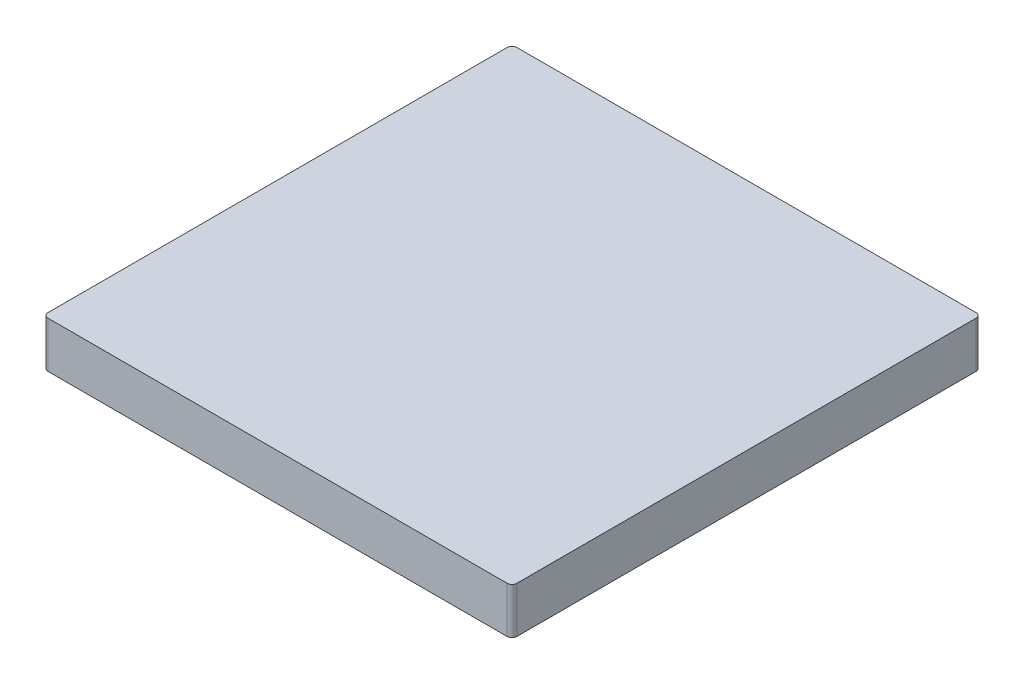
SolidWorks part; units mm, degrees
material "6061-T6 (SS)"
ref_plane "Front Plane" through (0, 0, 0) normal (0, 0, 1) x (1, 0, 0)
ref_plane "Top Plane" through (0, 0, 0) normal (0, 1, 0) x (1, 0, 0)
ref_plane "Right Plane" through (0, 0, 0) normal (1, 0, 0) x (0, 0, -1)
sketch "Sketch1" plane through (0, 0, 0) normal (0, 1, 0) x (1, 0, 0)
  line L1 (48.4125, -48.4125) -> (-48.4125, -48.4125)
  line L2 (48.4125, -48.4125) -> (48.4125, 48.4125)
  line L3 (48.4125, 48.4125) -> (-48.4125, 48.4125)
  line L4 (-48.4125, -48.4125) -> (-48.4125, 48.4125)
  line L5 (48.4125, -48.4125) -> (-48.4125, 48.4125) construction
  line L6 (48.4125, 48.4125) -> (-48.4125, -48.4125) construction
  point P0 (0, 0)
  dimension "D1" = 96.825
extrude "Boss-Extrude1" add sketch "Sketch1" along normal mid plane 9.525
fillet "Fillet1" radius 1 4 edges at (-48.4125, 0, -48.4125) (48.4125, 0, -48.4125) (48.4125, 0, 48.4125) (-48.4125, 0, 48.4125)
